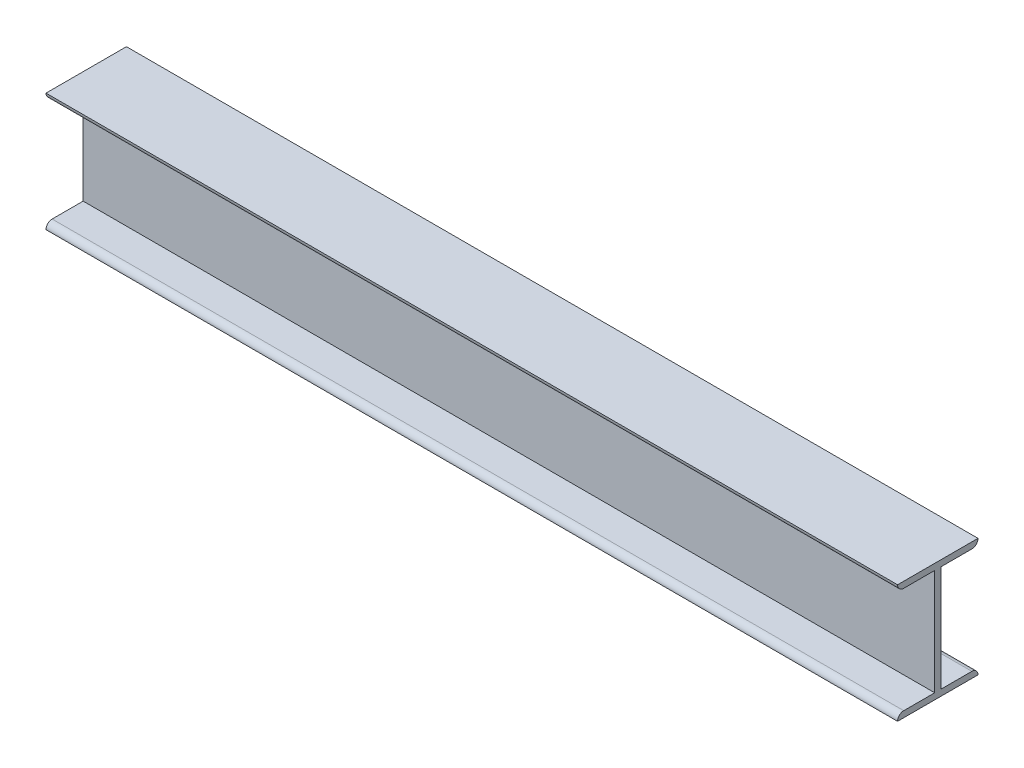
SolidWorks part; units mm, degrees
ref_plane "前视基准面" through (0, 0, 0) normal (0, 0, 1) x (1, 0, 0)
ref_plane "上视基准面" through (0, 0, 0) normal (0, 1, 0) x (1, 0, 0)
ref_plane "右视基准面" through (0, 0, 0) normal (1, 0, 0) x (0, 0, -1)
sketch "草图1" plane through (0, 0, 0) normal (0, 0, 1) x (1, 0, 0)
  line L1 (0, 250) -> (1800, 250)
  line L2 (0, 250) -> (0, 0)
  line L3 (0, 0) -> (1800, 0)
  line L4 (1800, 250) -> (1800, 0)
  dimension "D1" = 1800
  dimension "D2" = 250
extrude "拉伸1" add sketch "草图1" along normal blind 170
sketch "草图4" plane through (0, 0, 0) normal (-1, 0, 0) x (0, 0, 1)
  line L0 (170, 250) -> (0, 250) construction
  line L2 (0, 250) -> (0, 0) construction
  line L3 (0, 237) -> (78.5, 237)
  line L4 (0, 237) -> (0, 13)
  line L5 (0, 13) -> (78.5, 13)
  line L6 (78.5, 237) -> (78.5, 13)
  line L7 (170, 0) -> (0, 0) construction
  line L8 (170, 250) -> (170, 0) construction
  line L9 (170, 237) -> (91.5, 237)
  line L10 (170, 237) -> (170, 13)
  line L11 (170, 13) -> (91.5, 13)
  line L12 (91.5, 237) -> (91.5, 13)
  point P2 (85, 250)
  dimension "D1" = 13
  dimension "D2" = 6.5
  dimension "D3" = 13
extrude "切除-拉伸4" cut sketch "草图4" against normal through all
fillet "圆角1" radius 13 1 edges at (900, 13, 170)
fillet "圆角2" radius 13 1 edges at (900, 13, 0)
fillet "圆角3" radius 13 1 edges at (900, 237, 170)
fillet "圆角4" radius 13 1 edges at (900, 237, 0)
